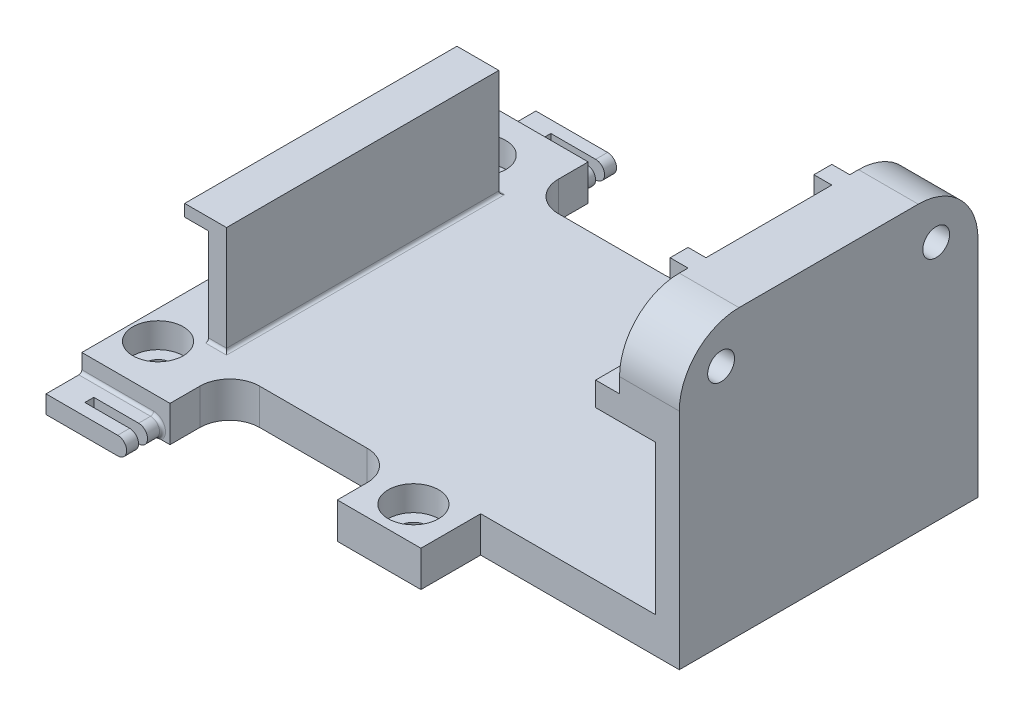
SolidWorks part; units mm, degrees
ref_plane "Front Plane" through (0, 0, 0) normal (0, 0, 1) x (1, 0, 0)
ref_plane "Top Plane" through (0, 0, 0) normal (0, 1, 0) x (1, 0, 0)
ref_plane "Right Plane" through (0, 0, 0) normal (1, 0, 0) x (0, 0, -1)
sketch "Sketch1" plane through (0, 0, 0) normal (0, 0, 1) x (1, 0, 0)
  line L0 (-14, 0) -> (0, 0)
  line L1 (0, 0) -> (0, -35)
  line L2 (0, -35) -> (-90, -35)
  line L3 (-90, -35) -> (-90, -29)
  line L4 (-90, -29) -> (-81, -29)
  line L5 (-78, -29) -> (-78, -11)
  line L7 (-85, -13) -> (-85, -11)
  line L8 (-85, -11) -> (-78, -11)
  line L10 (-78, -29) -> (-4, -29)
  line L11 (-4, -29) -> (-4, -4)
  line L12 (-4, -4) -> (-14, -4)
  line L13 (-14, -4) -> (-14, 0)
  line L15 (-81, -13) -> (-81, -29)
  line L16 (-85, -13) -> (-81, -13)
  dimension "D13" = 3
  dimension "D12" = 16
  dimension "D1" = 25
  dimension "D2" = 90
  dimension "D3" = 6
  dimension "D4" = 6
  dimension "D5" = 5
  dimension "D6" = 2
  dimension "D7" = 4
  dimension "D8" = 4
  dimension "D9" = 10
  dimension "D10" = 12
extrude "Extrude-Base" add sketch "Sketch1" along normal mid plane 70
sketch "Sketch2" plane through (0, -29, 0) normal (0, 1, 0) x (1, 0, 0)
  line L0 (0, 0) -> (-90, 0) construction
  line L1 (-90, -35) -> (-90, 35) construction
  line L2 (-4, -35) -> (-4, 35) construction
  circle A0 centre (-12, -10) radius 2.2
  circle A4 centre (-12, 10) radius 2.2
  circle A6 centre (-40.2447, 29.2506) radius 2.2479 construction
  circle A7 centre (-40.2447, 29.2506) radius 2.2479
  circle A8 centre (-40.2447, -29.2494) radius 2.2479 construction
  circle A9 centre (-40.2447, -29.2494) radius 2.2479
  circle A10 centre (-85.2447, 27.0006) radius 2.2 construction
  circle A11 centre (-85.2447, 27.0006) radius 2.2
  circle A12 centre (-85.2447, -26.9994) radius 2.2 construction
  circle A13 centre (-85.2447, -26.9994) radius 2.2
  dimension "D6" = 4.4
  dimension "D1" = 10
  dimension "D2" = 8
extrude "Cut-Bolt Holes" cut sketch "Sketch2" against normal blind 10
sketch "Sketch3" plane through (0, -29, 0) normal (0, 1, 0) x (1, 0, 0)
  line L0 (0, 0) -> (-78, 0) construction
  line L2 (-78, -35) -> (-78, 35) construction
  circle A2 centre (-12, -10) radius 4.215
  circle A3 centre (-40.2447, -29.2494) radius 4.215
  circle A4 centre (-85.2447, -26.9994) radius 4.215
  circle A5 centre (-12, -10) radius 2.2 construction
  circle A6 centre (-85.2447, 27.0006) radius 4.215
  circle A8 centre (-12, 10) radius 4.215
  circle A9 centre (-40.2447, 29.2494) radius 4.215
  circle A16 centre (-40.2447, -29.2494) radius 2.2479 construction
  dimension "D3" = 8.43
  dimension "D4" = 8.43
extrude "Cut-Bolt Head Insets" cut sketch "Sketch3" against normal blind 4.2 and the other way blind 13
sketch "Sketch4" plane through (-90, 0, 0) normal (-1, 0, 0) x (0, 0, 1)
  line L0 (35, -35) -> (-35, -35) construction
  line L1 (20, -35) -> (-20, -35)
  line L2 (20, -35) -> (20, -32)
  line L3 (20, -32) -> (-20, -32)
  line L4 (-20, -35) -> (-20, -32)
  point P7 (0, -35)
  point P8 (0, -35)
  dimension "D1" = 40
  dimension "D2" = 3
extrude "Cut-Top Clearance Slot" cut sketch "Sketch4" against normal blind 45
fillet "Fillet-Clearance Slot Pt 1" radius 3 2 edges at (-67.5, -32, 20) (-67.5, -32, -20)
fillet "Fillet-Clearance Slot Pt 2" radius 3 2 edges at (-67.5, -35, 20) (-67.5, -35, -20)
sketch "Sketch5" plane through (0, 0, 35) normal (0, 0, 1) x (1, 0, 0)
  line L0 (-78, -29) -> (-78, -11) construction
  line L1 (-78, -28.8827) -> (-78, -35) construction
  line L2 (-90, -35) -> (0, -35) construction
  line L3 (-78, -35) -> (-90, -35)
  line L4 (-90, -29) -> (-90, -35) construction
  line L5 (-90, -35) -> (-90, -32)
  line L6 (-90, -32) -> (-78, -32)
  arc A0 (-78, -35) -> (-78, -32) centre (-78, -33.5) ccw
  dimension "D1" = 3
extrude "Boss-Extrude1" add sketch "Sketch5" along normal blind 6
sketch "Sketch7" plane through (0, 0, -35) normal (0, 0, -1) x (-1, 0, 0)
  line L0 (78, -32) -> (90, -32)
  line L1 (90, -29) -> (90, -35) construction
  line L2 (90, -32) -> (90, -35)
  line L3 (90, -35) -> (78, -35)
  circle A0 centre (78, -33.5) radius 1.5 construction
  arc A1 (78, -32) -> (78, -35) centre (78, -33.5) ccw
extrude "Boss-Extrude2" add sketch "Sketch7" along normal blind 6
sketch "Sketch9" plane through (0, 0, 0) normal (1, 0, 0) x (0, 0, -1)
  line L1 (25.0006, 0) -> (-24.9994, 0)
  line L2 (25.0006, 0) -> (25.0006, 2.5)
  line L3 (15.0006, 12.5) -> (-14.9994, 12.5)
  line L4 (-24.9994, 0) -> (-24.9994, 2.5)
  line L5 (15.0006, 12.5) -> (-14.9994, 12.5) construction
  line L6 (15.0006, 12.5) -> (-14.9994, 12.5)
  line L7 (-35, 0) -> (35, 0) construction
  circle A2 centre (-17.9994, 5.5) radius 2.2479 construction
  circle A3 centre (-17.9994, 5.5) radius 2.2479
  circle A4 centre (18.0006, 5.5) radius 2.2479 construction
  circle A5 centre (18.0006, 5.5) radius 2.2479
  arc A6 (-14.9994, 12.5) -> (-24.9994, 2.5) centre (-14.9994, 2.5) ccw construction
  arc A7 (-14.9994, 12.5) -> (-24.9994, 2.5) centre (-14.9994, 2.5) ccw
  arc A8 (25.0006, 2.5) -> (15.0006, 12.5) centre (15.0006, 2.5) ccw construction
  arc A9 (25.0006, 2.5) -> (15.0006, 12.5) centre (15.0006, 2.5) ccw
extrude "Boss-Extrude3" add sketch "Sketch9" against normal blind 10 contours A7 L4 L1 L2 A9 L3 | A3 | A5
fillet "Fillet1" radius 0.5 4 edges at (-76.5, -33.5, 35) (-76.5, -33.5, -35) (-84, -32, 35) (-84, -32, -35)
sketch "Sketch10" plane through (0, -11, 0) normal (0, 1, 0) x (1, 0, 0)
  line L0 (-78, -35) -> (-85, -35) construction
  line L1 (-85, -35) -> (-78, -35)
  line L2 (-85, -35) -> (-85, -22.7844)
  line L3 (-85, -22.7844) -> (-78, -22.7844)
  line L4 (-78, -35) -> (-78, -22.7844)
  line L5 (-76.6771, 35) -> (0, 35) construction
  line L7 (-78, 0) -> (-85, 0) construction
  line L9 (-85, -35) -> (-85, 35) construction
  line L10 (-85, 22.7856) -> (-78, 22.7844)
  line L11 (-78, 35) -> (-78, 22.7844)
  line L12 (-85, 35) -> (-78, 35)
  line L13 (-85, 35) -> (-85, 22.7856)
  line L14 (-78, -35) -> (-78, 35) construction
  circle A0 centre (-85.2447, -26.9994) radius 4.215 construction
extrude "Cut-Extrude1" cut sketch "Sketch10" against normal up to surface (18 mm away) up to face at (-81.0297, -29, 26.9994)
fillet "Fillet2" radius 0.5 3 edges at (-79.5, -29, -22.7847) (-78, -29, 0) (-79.5, -29, 22.7844)
sketch "Sketch11" plane through (0, 0, 0) normal (0, 1, 0) x (1, 0, 0)
  line L0 (-10, -24.9994) -> (0, -24.9994) construction
  line L3 (0, -24.9994) -> (-33.2447, -24.9994)
  line L4 (-33.2447, -35.9994) -> (-33.2447, -24.9994)
  line L5 (0, 0) -> (-33.2447, 0) construction
  line L6 (0, 24.9994) -> (-33.2447, 24.9994)
  line L10 (0, 24.9994) -> (0, 35.9994)
  line L11 (0, 35.9994) -> (-33.2447, 35.9994)
  line L12 (-33.2447, 24.9994) -> (-33.2447, 35.9994)
  line L13 (-33.2447, -35.9994) -> (0, -35.9994)
  line L14 (0, -35.9994) -> (0, -24.9994)
  circle A2 centre (-40.2447, 29.2494) radius 4.215 construction
  dimension "D1" = 7
extrude "Cut-Extrude2" cut sketch "Sketch11" against normal up to surface (35 mm away)
sketch "Sketch13" plane through (0, -29, 0) normal (0, 1, 0) x (1, 0, 0)
  line L0 (-33.2447, -35) -> (-90, -35) construction
  line L1 (-75.2447, -35) -> (-47.2447, -35)
  line L2 (-75.2447, -35) -> (-75.2447, -24.9994)
  line L3 (-75.2447, -24.9994) -> (-47.2447, -24.9994)
  line L4 (-47.2447, -35) -> (-47.2447, -24.9994)
  line L5 (-33.2447, -35) -> (-33.2447, -24.9994) construction
  line L6 (-33.2447, -24.9994) -> (-4, -24.9994) construction
  line L7 (0, 0) -> (-90, 0) construction
  line L8 (-90, -35) -> (-90, 35) construction
  line L9 (-75.2447, 24.9994) -> (-47.2447, 24.9994)
  line L10 (-47.2447, 35) -> (-47.2447, 24.9994)
  line L11 (-75.2447, 35) -> (-47.2447, 35)
  line L12 (-75.2447, 35) -> (-75.2447, 24.9994)
  dimension "D1" = 14
  dimension "D2" = 28
extrude "Cut-Extrude5" cut sketch "Sketch13" against normal up to surface (6 mm away) up to face at (-58.2163, -35, 0)
fillet "Fillet3" radius 5 4 edges at (-75.2447, -32, -24.9994) (-47.2447, -32, -24.9994) (-47.2447, -32, 24.9994) (-75.2447, -32, 24.9994)
sketch "Sketch14" plane through (-10, 0, 0) normal (-1, 0, 0) x (0, 0, 1)
  line L0 (24.9994, 0) -> (-24.9994, 0) construction
  line L1 (17.9994, 10.5417) -> (13.6332, 8.0209) construction
  line L2 (13.6332, 8.0209) -> (13.6332, 2.9791) construction
  line L3 (13.6332, 2.9791) -> (17.9994, 0.4583) construction
  line L4 (17.9994, 0.4583) -> (22.3657, 2.9791) construction
  line L5 (22.3657, 2.9791) -> (22.3657, 8.0209) construction
  line L6 (22.3657, 8.0209) -> (17.9994, 10.5417) construction
  line L7 (-18.0006, 10.5417) -> (-22.3668, 8.0209) construction
  line L8 (-22.3668, 8.0209) -> (-22.3668, 2.9791) construction
  line L9 (-22.3668, 2.9791) -> (-18.0006, 0.4583) construction
  line L10 (-18.0006, 0.4583) -> (-13.6343, 2.9791) construction
  line L11 (-13.6343, 2.9791) -> (-13.6343, 8.0209) construction
  line L12 (-13.6343, 8.0209) -> (-18.0006, 10.5417) construction
  line L13 (13.5332, 0) -> (13.5332, 12.5)
  line L14 (-24.9994, 0) -> (24.9994, 0) construction
  line L15 (-15.0006, 12.5) -> (14.9994, 12.5) construction
  line L16 (13.5332, 12.5) -> (10.5332, 12.5)
  line L17 (10.5332, 12.5) -> (10.5332, 0)
  line L18 (10.5332, 0) -> (13.5332, 0)
  line L19 (0, 0) -> (0, 12.3551) construction
  line L20 (-10.5332, 12.5) -> (-10.5332, 0)
  line L21 (-13.5332, 12.5) -> (-10.5332, 12.5)
  line L22 (-13.5332, 0) -> (-13.5332, 12.5)
  line L23 (-10.5332, 0) -> (-13.5332, 0)
  circle A0 centre (17.9994, 5.5) radius 4.3663 construction
  circle A1 centre (-18.0006, 5.5) radius 4.3663 construction
  dimension "D1" = 8.7325
  dimension "D2" = 0.2
  dimension "D3" = 3
extrude "Boss-Extrude4" add sketch "Sketch14" along normal blind 3
sketch "Sketch15" plane through (0, -32, 0) normal (0, 1, 0) x (1, 0, 0)
  line L0 (-85.5, -39) -> (-85.5, -37.5)
  line L2 (-85.5, -37.5) -> (-76.5, -37.5)
  line L3 (-76.5, -41) -> (-76.5, -35.5) construction
  line L4 (-76.5, -37.5) -> (-76.5, -39)
  line L5 (-76.5, -39) -> (-85.5, -39)
  line L6 (-78, -41) -> (-78, -35.5) construction
  point P4 (-78, -38.25)
  point P5 (-85.5, -38.25)
  dimension "D1" = 9
  dimension "D2" = 1.5
  dimension "D3" = 9
  dimension "D4" = 0
extrude "Cut-Extrude6" cut sketch "Sketch15" against normal blind 10
mirror "Mirror1" about plane through (0, 0, 0) normal (0, 0, 1) of "Cut-Extrude6"
sketch "Sketch16" plane through (-10, 0, 0) normal (-1, 0, 0) x (0, 0, 1)
  line L1 (-18.0006, 0.4) -> (-13.5838, 2.95)
  line L2 (-13.5838, 2.95) -> (-13.5838, 8.05)
  line L3 (-13.5838, 8.05) -> (-18.0006, 10.6)
  line L4 (-18.0006, 10.6) -> (-22.4173, 8.05)
  line L5 (-22.4173, 8.05) -> (-22.4173, 2.95)
  line L6 (-22.4173, 2.95) -> (-18.0006, 0.4)
  line L7 (0, -26.125) -> (0, 26.125) construction
  line L8 (22.4173, 2.95) -> (18.0006, 0.4)
  line L9 (22.4173, 8.05) -> (22.4173, 2.95)
  line L10 (18.0006, 10.6) -> (22.4173, 8.05)
  line L11 (13.5838, 8.05) -> (18.0006, 10.6)
  line L12 (13.5838, 2.95) -> (13.5838, 8.05)
  line L13 (18.0006, 0.4) -> (13.5838, 2.95)
  circle A0 centre (-18.0006, 5.5) radius 4.4167 construction
  circle A1 centre (18.0006, 5.5) radius 4.4167 construction
  dimension "D1" = 5.1
extrude "Cut-Extrude7" cut sketch "Sketch16" against normal blind 6
equation "\"holeBoltDiam\"=4.4"
equation "\"D6@Sketch2\"=\"holeBoltDiam\""
equation "\"insetBoltHead\"=8.43"
equation "\"D3@Sketch3\"=\"insetBoltHead\""
equation "\"D4@Sketch3\"=\"insetBoltHead\""
